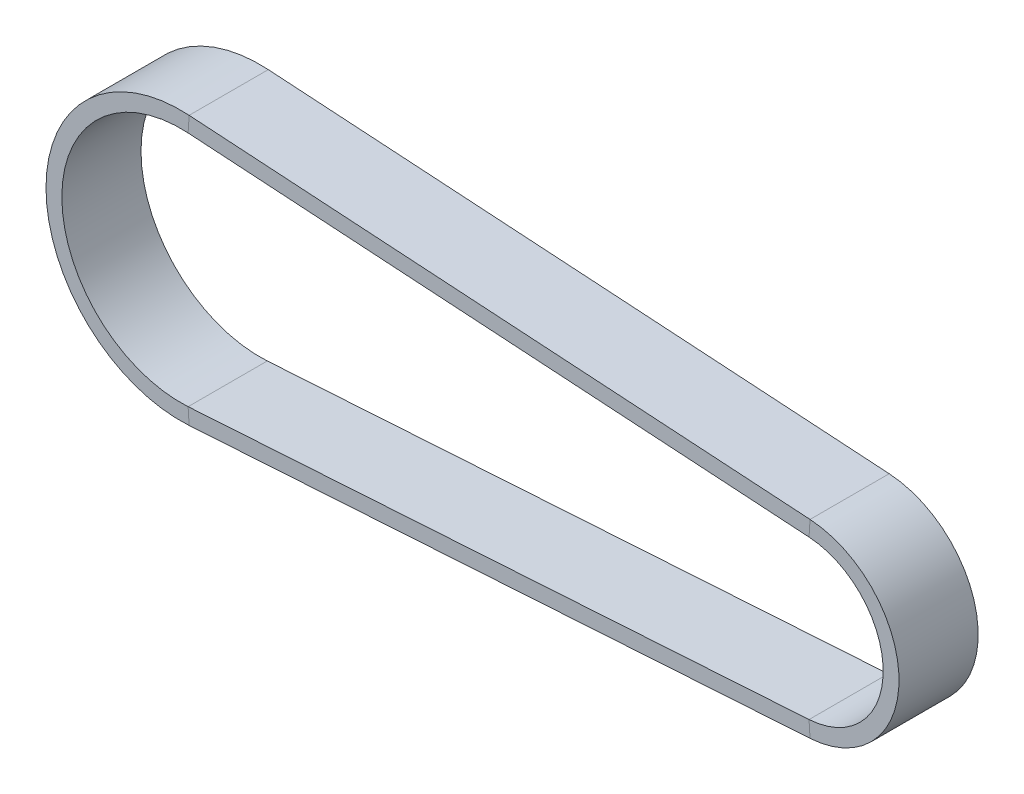
SolidWorks part; units mm, degrees
ref_plane "Ebene vorne" through (0, 0, 0) normal (0, 0, 1) x (1, 0, 0)
ref_plane "Ebene oben" through (0, 0, 0) normal (0, 1, 0) x (1, 0, 0)
ref_plane "Ebene rechts" through (0, 0, 0) normal (1, 0, 0) x (0, 0, -1)
sketch "Skizze2" plane through (0, 0, 0) normal (0, 1, 0) x (1, 0, 0)
  line L0 (-15, -20.5) -> (-17, -20.5) construction
  line L1 (-17, -10.5) -> (-17, -20.5) construction
  line L2 (-15, -10.5) -> (-17, -10.5) construction
  line L3 (-15, -10.5) -> (-15, -20.5) construction
  line L4 (-15, -20.5) -> (-17, -20.5)
  line L5 (-17, -10.5) -> (-17, -20.5)
  line L6 (-15, -10.5) -> (-17, -10.5)
  line L7 (-15, -10.5) -> (-15, -20.5)
ref_plane "Ebene1" through (0, 0, 15.5) normal (0, 0, 1) x (1, 0, 0)
sketch "Skizze3" plane through (0, 0, 15.5) normal (0, 0, 1) x (1, 0, 0)
  line L1 (0, 0) -> (-25, 0) construction
  line L2 (0, 0) -> (450, 0) construction
  line L3 (0.9524, 14.9697) -> (79.3849, 9.9798)
  arc A1 (-15, 0) -> (0.9524, 14.9697) centre (0, 0) cw
  arc A3 (88.75, 0) -> (79.3849, 9.9798) centre (78.75, 0) ccw
  dimension "D1" = 10
  dimension "D2" = 15
sweep "Austragung1" add profiles "Skizze2" path "Skizze3"
mirror "Spiegeln1" about plane through (0, 0, 0) normal (0, -1, 0) of bodies 101
